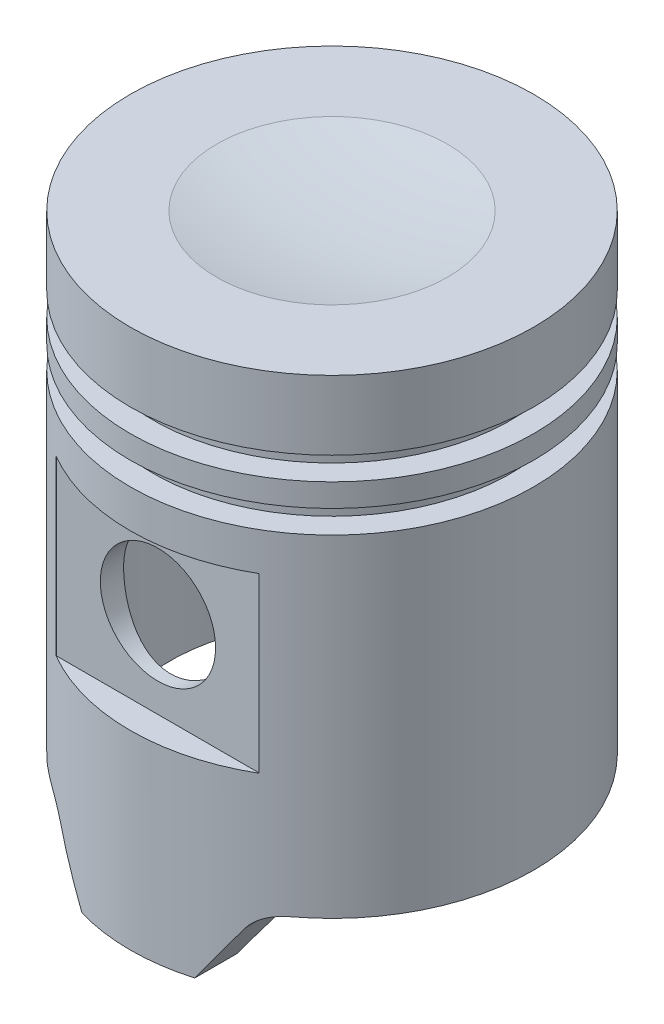
SolidWorks part; units mm, degrees
ref_plane "Front Plane" through (0, 0, 0) normal (0, 0, 1) x (1, 0, 0)
ref_plane "Top Plane" through (0, 0, 0) normal (0, 1, 0) x (1, 0, 0)
ref_plane "Right Plane" through (0, 0, 0) normal (1, 0, 0) x (0, 0, -1)
sketch "Sketch1" plane through (0, 0, 0) normal (0, 0, 1) x (1, 0, 0)
  line L0 (0, 0) -> (0, 50.546)
  line L1 (12.7127, 51.816) -> (22.225, 51.816)
  line L2 (22.225, 51.816) -> (22.225, 44.196)
  line L3 (22.225, 44.196) -> (19.685, 44.196)
  line L4 (19.685, 44.196) -> (19.685, 41.656)
  line L5 (19.685, 41.656) -> (22.225, 41.656)
  line L6 (22.225, 41.656) -> (22.225, 39.116)
  line L7 (22.225, 39.116) -> (19.685, 39.116)
  line L8 (19.685, 39.116) -> (19.685, 36.576)
  line L9 (19.685, 36.576) -> (22.225, 36.576)
  line L10 (22.225, 36.576) -> (22.225, 0)
  line L11 (22.225, 0) -> (0, 0)
  arc A0 (0, 50.546) -> (12.7127, 51.816) centre (0, 114.808) ccw
  dimension "D12" = 64.262
  dimension "D2" = 7.62
  dimension "D3" = 2.54
  dimension "D4" = 2.54
  dimension "D5" = 2.54
  dimension "D6" = 2.54
  dimension "D7" = 2.54
  dimension "D8" = 22.225
  dimension "D9" = 51.816
  dimension "D10" = 36.576
  dimension "D11" = 1.27
revolve "Revolve1" add sketch "Sketch1" angle 360 about L0
ref_plane "Plane1" through (0, 0, 22.225) normal (0, 0, 1) x (1, 0, 0)
sketch "Sketch2" plane through (0, 0, 22.225) normal (0, 0, 1) x (1, 0, 0)
  line L0 (-22.225, 0) -> (22.225, 0) construction
  line L1 (-11.176, 13.335) -> (11.176, 13.335)
  line L2 (-11.176, 13.335) -> (-11.176, 32.385)
  line L3 (-11.176, 32.385) -> (11.176, 32.385)
  line L4 (11.176, 13.335) -> (11.176, 32.385)
  line L5 (-11.176, 13.335) -> (11.176, 32.385) construction
  line L6 (-11.176, 32.385) -> (11.176, 13.335) construction
  line L7 (-22.225, 36.576) -> (-22.225, 0) construction
  circle A0 centre (0, 22.86) radius 6.35
  point P0 (0, 22.86)
  dimension "D2" = 12.7
  dimension "D1" = 19.05
  dimension "D3" = 22.352
  dimension "D4" = 22.86
  dimension "D5" = 11.049
extrude "Cut-Extrude2" cut sketch "Sketch2" against normal through all contours A0
extrude "Cut-Extrude3" cut sketch "Sketch2<4>" against normal blind 3.048
sketch "Sketch2<4>" plane through (0, 0, 22.225) normal (0, 0, 1) x (1, 0, 0) same geometry as "Sketch2"
mirror "Mirror1" about plane through (0, 0, 0) normal (0, 0, 1) of "Cut-Extrude3"
sketch "Sketch3" plane through (0, 0, 0) normal (0, -1, 0) x (1, 0, 0)
  circle A0 centre (0, 0) radius 17.78
  dimension "D1" = 35.56
extrude "Cut-Extrude4" cut sketch "Sketch3" against normal blind 36.576
sketch "Sketch4" plane through (0, 0, 0) normal (0, -1, 0) x (1, 0, 0)
  line L0 (-13.335, 17.78) -> (-13.335, 11.7604)
  line L1 (13.335, 17.78) -> (13.335, 11.7604)
  line L2 (0, 22.225) -> (0, -22.225) construction
  line L3 (-22.225, 0) -> (22.225, 0) construction
  circle A0 centre (0, 0) radius 22.225 construction
  circle A1 centre (0, 0) radius 17.78 construction
  arc A2 (-13.335, 17.78) -> (13.335, 17.78) centre (0, 0) cw
  arc A3 (-13.335, 11.7604) -> (13.335, 11.7604) centre (0, 0) cw
  dimension "D2" = 17.78
  dimension "D3" = 22.225
  dimension "D1" = 8.89
extrude "Boss-Extrude1" add sketch "Sketch4" along normal blind 7.62
sketch "Sketch5" plane through (0, 0, 22.225) normal (0, 0, 1) x (1, 0, 0)
  line L0 (-13.335, -7.62) -> (-13.335, 0) construction
  line L1 (-6.2153, -7.62) -> (-10.207, -1.6347)
  line L2 (-13.335, -7.62) -> (13.335, -7.62) construction
  line L3 (-6.2153, -7.62) -> (-13.335, -7.62)
  line L4 (-13.335, -7.62) -> (-13.335, 0)
  arc A0 (-10.207, -1.6347) -> (-13.335, 0) centre (-13.335, -3.81) ccw
  dimension "D1" = 236.3
  dimension "D2" = 3.81
  dimension "D3" = 7.1197
extrude "Cut-Extrude5" cut sketch "Sketch5" against normal blind 12.7
mirror "Mirror2" about plane through (0, 0, 0) normal (1, 0, 0) of "Cut-Extrude5"
mirror "Mirror3" about plane through (0, 0, 0) normal (0, 0, 1) of "Mirror2", "Cut-Extrude5", "Boss-Extrude1"
